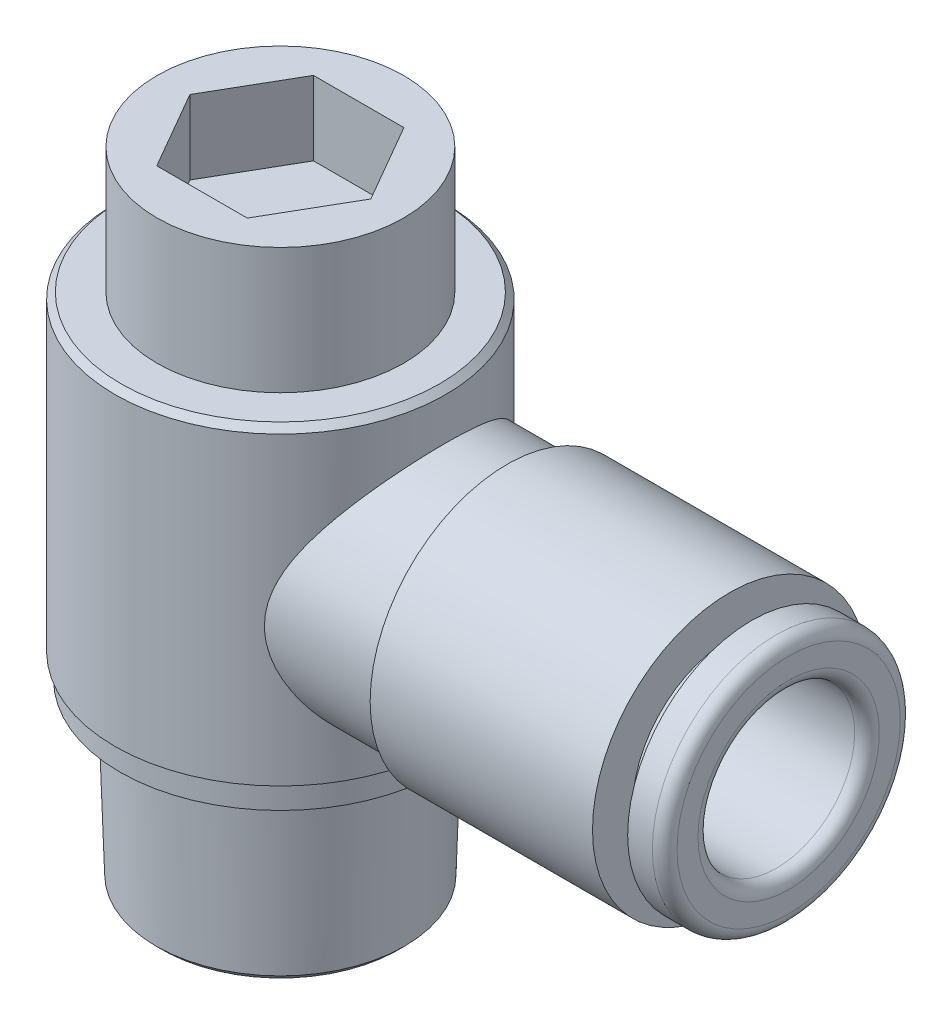
SolidWorks part; units mm, degrees
ref_plane "Front" through (0, 0, 0) normal (0, 0, 1) x (1, 0, 0)
ref_plane "Top" through (0, 0, 0) normal (0, 1, 0) x (1, 0, 0)
ref_plane "Right" through (0, 0, 0) normal (1, 0, 0) x (0, 0, -1)
ref_plane "L2-Center_2_Thread" through (0, -13.7, 0) normal (0, 1, 0) x (-1, 0, 0)
ref_plane "Thread_Height" through (0, -6.6, 0) normal (0, 1, 0) x (-1, 0, 0)
ref_plane "CBody_Bottom" through (0, -5.6, 0) normal (0, 1, 0) x (-1, 0, 0)
ref_plane "CBody_Top" through (0, 7, 0) normal (0, 1, 0) x (-1, 0, 0)
ref_plane "L3-Center_Height" through (0, 12.1, 0) normal (0, 1, 0) x (-1, 0, 0)
ref_plane "L1-Length" through (20.6, 0, 0) normal (1, 0, 0) x (0, 0, -1)
ref_plane "Release_Height" through (18.2, 0, 0) normal (1, 0, 0) x (0, 0, -1)
ref_plane "RBody_Height" through (8.9, 0, 0) normal (1, 0, 0) x (0, 0, -1)
ref_plane "M-Tube_Depth" through (7.3, 0, 0) normal (1, 0, 0) x (0, 0, -1)
sketch "CBody_Sketch" plane through (0, 0, 0) normal (0, 1, 0) x (1, 0, 0)
  circle A0 centre (0, 0) radius 6.7
  dimension "Dia" = 13.4
extrude "CBody" add sketch "CBody_Sketch" along normal up to surface (7 mm away) and the other way up to surface (5.6 mm away) up to plane "CBody_Top" other way up to plane "CBody_Bottom"
chamfer "CBody_Chamfer" distance 0.25 angle 45 1 edges at (0, 7, 6.7)
sketch "Thread_Offset_Sketch" plane through (0, -5.6, 0) normal (0, 1, 0) x (-1, 0, 0)
  circle A0 centre (0, 0) radius 6.5
  dimension "Dia" = 13
extrude "Thread_Offset" add sketch "Thread_Offset_Sketch" against normal up to surface (1 mm away) up to plane "Thread_Height"
sketch "Thread_Sketch" plane through (0, 0, 0) normal (0, 0, 1) x (1, 0, 0)
  line L0 (0, 0) -> (0, -11.5232) construction
  line L1 (0, 6.75) -> (0, -5.6) construction
  line L2 (-5.2473, -6.6) -> (-5.0266, -13.7)
  line L3 (-5.0266, -13.7) -> (0, -13.7)
  line L4 (0, -13.7) -> (0, -6.6)
  line L5 (0, -6.6) -> (-5.2473, -6.6)
  line L6 (12.1153, -6.6) -> (-12.1153, -6.6) construction
  line L7 (12.1153, -13.7) -> (-12.1153, -13.7) construction
  point P13 (-5.15, -9.73)
  dimension "Taper" = 88.22
  dimension "a" = 3.97
  dimension "d" = 10.3
revolve "Thread" add sketch "Thread_Sketch" angle 360 about L0
chamfer "Thread_Chamfer" distance 0.25 angle 45 1 edges at (0, -13.7, 5.0266) first distance on face at (0, -13.7, 5.0266)
sketch "Head_Sketch" plane through (0, 7, 0) normal (0, 1, 0) x (-1, 0, 0)
  circle A0 centre (0, 0) radius 5
  dimension "Dia" = 10
extrude "Head" add sketch "Head_Sketch" along normal up to surface (5.1 mm away) up to plane "L3-Center_Height"
sketch "Hex_Sketch" plane through (0, 12.1, 0) normal (0, 1, 0) x (-1, 0, 0)
  line L1 (-1.8331, 3.175) -> (-3.6662, 0)
  line L2 (-3.6662, 0) -> (-1.8331, -3.175)
  line L3 (-1.8331, -3.175) -> (1.8331, -3.175)
  line L4 (1.8331, -3.175) -> (3.6662, 0)
  line L5 (3.6662, 0) -> (1.8331, 3.175)
  line L6 (1.8331, 3.175) -> (-1.8331, 3.175)
  circle A0 centre (0, 0) radius 3.175 construction
  dimension "Flats" = 6.35
extrude "Hex" cut sketch "Hex_Sketch" against normal blind 3
sketch "RBody_Sketch" plane through (0, 0, 0) normal (0, 1, 0) x (1, 0, 0)
  line L1 (-16.3355, 0) -> (14.6433, 0) construction
  line L2 (0, 0) -> (2.9156, -5.05)
  line L3 (2.9156, -5.05) -> (8.9, -5.05)
  line L4 (8.9, -5.05) -> (9.1887, -5.55)
  line L5 (9.1887, -5.55) -> (18.2, -5.55)
  line L6 (18.2, -5.55) -> (18.2, 0)
  line L7 (18.2, 0) -> (0, 0)
  line L8 (8.9, -50) -> (8.9, 50) construction
  line L9 (18.2, -50) -> (18.2, 50) construction
  dimension "smDia" = 10.1
  dimension "lgDia" = 11.1
  dimension "Angle" = 60
revolve "RBody" add sketch "RBody_Sketch" angle 360 about L1
sketch "Release_Sketch" plane through (0, 0, 0) normal (0, 1, 0) x (1, 0, 0)
  line L0 (0, 0) -> (22.0979, 0) construction
  line L2 (18.2, 0) -> (18.2, 3.925)
  line L3 (18.2, 3.925) -> (19.1, 3.925)
  line L4 (19.1, 3.925) -> (19.1, 5.025)
  line L5 (19.1, 5.025) -> (20.1, 5.025)
  line L6 (20.6, 4.525) -> (20.6, 0)
  line L7 (20.6, 0) -> (18.2, 0)
  line L8 (18.2, -50) -> (18.2, 50) construction
  line L9 (20.6, -50) -> (20.6, 50) construction
  line L10 (-16.3355, 0) -> (14.6433, 0) construction
  arc A0 (20.6, 4.525) -> (20.1, 5.025) centre (20.1, 4.525) ccw
  point P17 (20.6, 5.025)
  dimension "Radius" = 0.5
  dimension "Outer_Dia" = 10.05
  dimension "Tube_Dia" = 7.85
  dimension "Thickness" = 1.5
revolve "Release" add sketch "Release_Sketch" angle 360 about L0
sketch "Sketch1" plane through (0, -6.6, 0) normal (0, -1, 0) x (1, 0, 0)
  circle A0 centre (0, 0) radius 3.75
  dimension "D1" = 7.5
extrude "Gasket" [suppressed] add sketch "Sketch1" along normal blind 0.4
sketch "Tube_Sketch" plane through (20.6, 0, 0) normal (1, 0, 0) x (0, 0, -1)
  circle A0 centre (0, 0) radius 3.175
  dimension "Dia" = 6.35
extrude "Tube" cut sketch "Tube_Sketch" against normal up to surface (13.3 mm away) up to plane "M-Tube_Depth"
fillet "Tube_Fillet" radius 0.5 1 edges at (20.6, 0, -3.175)
sketch "Path Port" plane through (0, 0, 0) normal (0, 0, 1) x (1, 0, 0)
  line L0 (20.6, 0) -> (2, 0)
  line L1 (0, -2) -> (0, -13.7)
  line L2 (12.1153, -13.7) -> (-12.1153, -13.7) construction
  line L3 (20.6, -50) -> (20.6, 50) construction
  arc A0 (0, -2) -> (2, 0) centre (2, -2) cw
  point P10 (0, 0)
  dimension "Radius" = 2
sketch "Profile Port" plane through (20.6, 0, 0) normal (1, 0, 0) x (0, 0, -1)
  circle A0 centre (0, 0) radius 1.5875
  dimension "Dia" = 3.175
sweep "Port" cut profiles "Profile Port" path "Path Port"
sketch "Connecting Point" plane through (0, 0, 0) normal (0, 0, 1) x (1, 0, 0)
  line L0 (12.1153, 12.1) -> (-12.1153, 12.1) construction
  point P0 (0, -10.5)
  dimension "A" = 22.6
